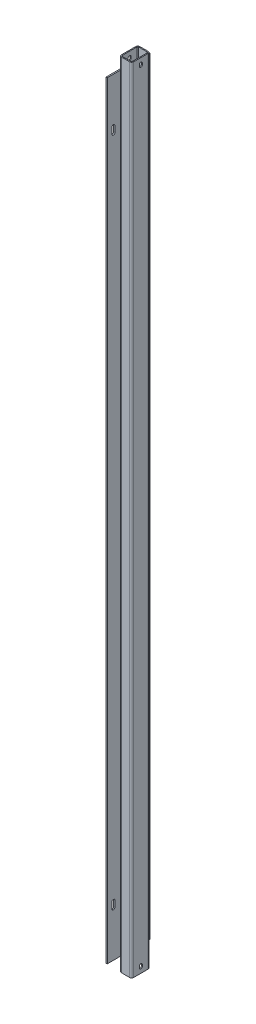
SolidWorks part; units mm, degrees
ref_plane "前视基准面" through (0, 0, 0) normal (0, 0, 1) x (1, 0, 0)
ref_plane "上视基准面" through (0, 0, 0) normal (0, 1, 0) x (1, 0, 0)
ref_plane "右视基准面" through (0, 0, 0) normal (1, 0, 0) x (0, 0, -1)
sketch "草图1" plane through (0, 0, 0) normal (0, 0, 1) x (1, 0, 0)
  line L0 (0, 1300) -> (0, -1300)
  line L1 (0, 0) -> (63.8736, 0) construction
  dimension "D1" = 2600
other "结构构件1" corner treatment miter
ref_plane "基准面1" through (0, 1300, 0) normal (0, -1, 0) x (1, 0, 0)
sketch "Sketch1" plane through (0, 1300, 0) normal (0, -1, 0) x (1, 0, 0)
  line L0 (-13.6, -26.8) -> (13.6, -26.8)
  line L1 (-16.8, -23.6) -> (-16.8, 23.6)
  line L2 (13.6, 26.8) -> (-13.6, 26.8)
  line L3 (16.8, 23.6) -> (16.8, -23.6)
  line L4 (-13.6, -30) -> (13.6, -30)
  line L5 (-20, -23.6) -> (-20, 23.6)
  line L6 (13.6, 30) -> (-13.6, 30)
  line L7 (20, 23.6) -> (20, -23.6)
  arc A0 (20, 23.6) -> (13.6, 30) centre (13.6, 23.6) ccw
  arc A1 (13.6, -30) -> (20, -23.6) centre (13.6, -23.6) ccw
  arc A2 (-20, -23.6) -> (-13.6, -30) centre (-13.6, -23.6) ccw
  arc A3 (-13.6, 30) -> (-20, 23.6) centre (-13.6, 23.6) ccw
  arc A4 (-13.6, 26.8) -> (-16.8, 23.6) centre (-13.6, 23.6) ccw
  arc A5 (16.8, 23.6) -> (13.6, 26.8) centre (13.6, 23.6) ccw
  arc A6 (13.6, -26.8) -> (16.8, -23.6) centre (13.6, -23.6) ccw
  arc A7 (-16.8, -23.6) -> (-13.6, -26.8) centre (-13.6, -23.6) ccw
  point P0 (0, 30)
  point P1 (20, 0)
  point P2 (0, -30)
  point P3 (-20, 0)
  point P4 (-20, 30)
  point P5 (20, 30)
  point P6 (20, -30)
  point P7 (-20, -30)
  point P8 (0, 0)
  point P33 (0, 0)
  dimension "D1" = 6.4
  dimension "Thickness" = 3.2
  dimension "V_leg" = 60
  dimension "H_leg" = 40
sketch "草图3" plane through (-20, 0, 0) normal (-1, 0, 0) x (0, 0, 1)
  line L0 (0, -1300) -> (0, -1384.9914) construction
  line L1 (-70, 1258) -> (70, 1258)
  line L2 (-70, 1258) -> (-70, -1258)
  line L3 (-70, -1258) -> (70, -1258)
  line L4 (70, 1258) -> (70, -1258)
  line L5 (23.6, -1300) -> (-23.6, -1300) construction
  line L6 (23.6, 1300) -> (-23.6, 1300) construction
  dimension "D1" = 140
  dimension "D2" = 42
  dimension "D3" = 42
sheet metal parameters "钣金1" thickness 4 parameters "D1"=1
base flange "基体-法兰1" sketch "草图3" thickness 4 reverse thickness direction yes parameters "D1"=1
sketch "草图4" plane through (20, 0, 0) normal (1, 0, 0) x (0, 0, -1)
  line L2 (0, -1282.5) -> (0, -1277.5) construction
  line L3 (-5, -1282.5) -> (-5, -1277.5)
  line L4 (5, -1282.5) -> (5, -1277.5)
  line L5 (23.6, -1300) -> (-23.6, -1300) construction
  line L6 (0, 1277.5) -> (0, 1282.5) construction
  line L7 (-5, 1277.5) -> (-5, 1282.5)
  line L8 (5, 1277.5) -> (5, 1282.5)
  line L10 (23.6, 1300) -> (-23.6, 1300) construction
  arc A0 (-5, -1282.5) -> (5, -1282.5) centre (0, -1282.5) ccw
  arc A1 (5, -1277.5) -> (-5, -1277.5) centre (0, -1277.5) ccw
  arc A2 (-5, 1277.5) -> (5, 1277.5) centre (0, 1277.5) ccw
  arc A3 (5, 1282.5) -> (-5, 1282.5) centre (0, 1282.5) ccw
  point P2 (0, -1280)
  point P13 (0, 1280)
  dimension "D1" = 5
  dimension "D2" = 5
  dimension "D5" = 5
  dimension "D3" = 20
  dimension "D4" = 5
  dimension "D6" = 20
extrude "切除-拉伸1" cut sketch "草图4" against normal through all normal cut yes
sketch "草图8" plane through (-24, 0, 0) normal (-1, 0, 0) x (0, 0, 1)
  line L0 (50, 1110) -> (50, 1090) construction
  line L1 (55, 1110) -> (55, 1090)
  line L2 (45, 1110) -> (45, 1090)
  line L3 (50, -1090) -> (50, -1110) construction
  line L4 (55, -1090) -> (55, -1110)
  line L5 (45, -1090) -> (45, -1110)
  line L6 (0, 0) -> (0, -116.366) construction
  line L7 (-50, -1090) -> (-50, -1110) construction
  line L8 (-55, -1090) -> (-55, -1110)
  line L9 (-45, -1090) -> (-45, -1110)
  line L10 (-50, 1110) -> (-50, 1090) construction
  line L11 (-55, 1110) -> (-55, 1090)
  line L12 (-45, 1110) -> (-45, 1090)
  arc A0 (55, 1110) -> (45, 1110) centre (50, 1110) ccw
  arc A1 (45, 1090) -> (55, 1090) centre (50, 1090) ccw
  arc A2 (55, -1090) -> (45, -1090) centre (50, -1090) ccw
  arc A3 (45, -1110) -> (55, -1110) centre (50, -1110) ccw
  arc A4 (-55, -1090) -> (-45, -1090) centre (-50, -1090) cw
  arc A5 (-45, -1110) -> (-55, -1110) centre (-50, -1110) cw
  arc A6 (-55, 1110) -> (-45, 1110) centre (-50, 1110) cw
  arc A7 (-45, 1090) -> (-55, 1090) centre (-50, 1090) cw
  point P2 (50, 1100)
  point P9 (50, -1100)
  point P21 (-50, -1100)
  point P28 (-50, 1100)
  dimension "D2" = 5
  dimension "D4" = 5
  dimension "D1" = 20
  dimension "D3" = 20
extrude "切除-拉伸5" cut sketch "草图8" against normal blind 499 normal cut yes
flat pattern "平板型式1" [suppressed]
sketch "折弯-线1" plane through (0, 0, 0) normal (0, 1, 0) x (-1, 0, 0)
